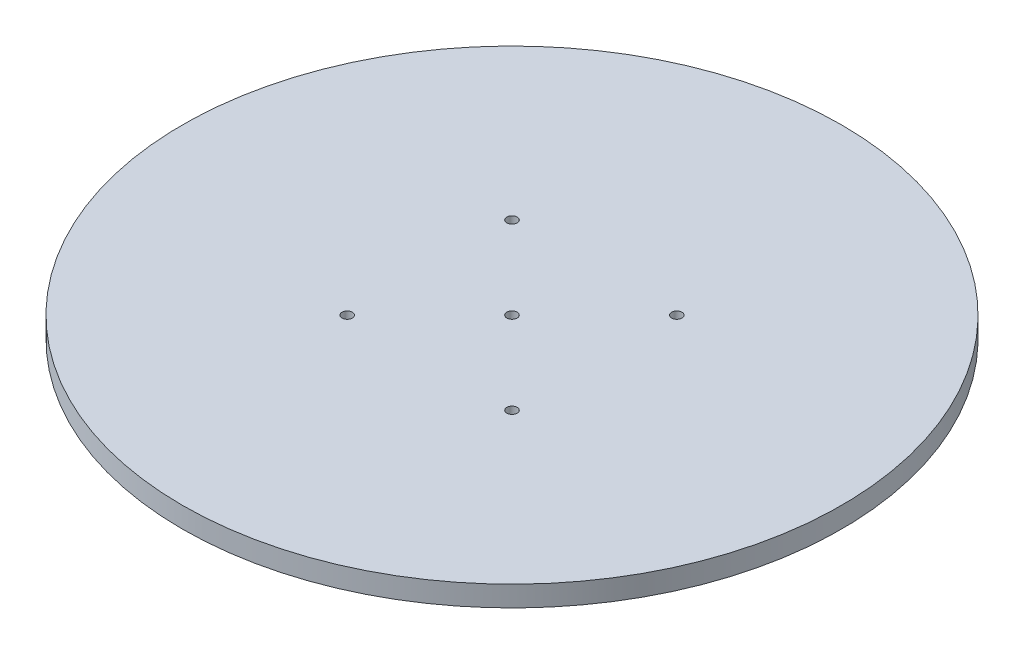
SolidWorks part; units mm, degrees
ref_plane "Front Plane" through (0, 0, 0) normal (0, 0, 1) x (1, 0, 0)
ref_plane "Top Plane" through (0, 0, 0) normal (0, 1, 0) x (1, 0, 0)
ref_plane "Right Plane" through (0, 0, 0) normal (1, 0, 0) x (0, 0, -1)
sketch "Sketch1" plane through (0, 0, 0) normal (0, 1, 0) x (1, 0, 0)
  circle A0 centre (0, 0) radius 127
  dimension "D1" = 254
extrude "Boss-Extrude1" add sketch "Sketch1" along normal blind 7.9375
hole_wizard "5/32 (0.15625) Diameter Hole2" positions "Sketch4" profile "Sketch5" hole size "5/32" standard "ANSI Inch" end condition through all
sketch "Sketch4" plane through (0, 7.9375, 0) normal (0, 1, 0) x (1, 0, 0)
  line L1 (-31.75, -31.75) -> (31.75, -31.75) construction
  line L2 (-31.75, -31.75) -> (-31.75, 31.75) construction
  line L3 (-31.75, 31.75) -> (31.75, 31.75) construction
  line L4 (31.75, -31.75) -> (31.75, 31.75) construction
  line L5 (-31.75, -31.75) -> (31.75, 31.75) construction
  line L6 (-31.75, 31.75) -> (31.75, -31.75) construction
  point P2 (31.75, 31.75)
  point P31 (-31.75, -31.75)
  point P32 (-31.75, 31.75)
  point P33 (31.75, -31.75)
  point P46 (0, 0)
  dimension "D1" = 63.5
sketch "Sketch5" plane through (31.75, 7.9375, -31.75) normal (1, 0, 0) x (0, 0, 1)
  line L0 (0, 0) -> (0, 7.9375)
  line L1 (0, 7.9375) -> (1.9844, 7.9375)
  line L2 (1.9844, 7.9375) -> (1.9844, 0)
  line L5 (1.9844, 0) -> (0, 0)
  line L11 (0, -6.35) -> (0, 107.95) construction
  dimension "Thru Hole Dia." = 3.9688
  dimension "Thru Hole Depth" = 7.9375
